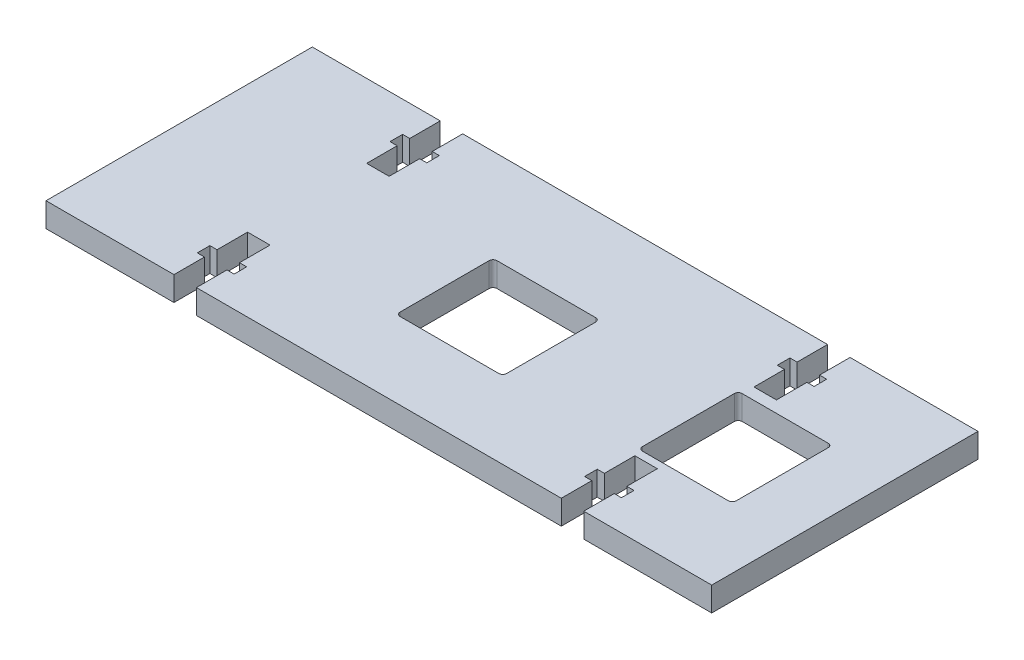
SolidWorks part; units mm, degrees
ref_plane "Front Plane" through (0, 0, 0) normal (0, 0, 1) x (1, 0, 0)
ref_plane "Top Plane" through (0, 0, 0) normal (0, 1, 0) x (1, 0, 0)
ref_plane "Right Plane" through (0, 0, 0) normal (1, 0, 0) x (0, 0, -1)
sketch "Sketch1" plane through (0, 0, 0) normal (0, 1, 0) x (1, 0, 0)
  line L1 (-43.6562, -17.4625) -> (43.6563, -17.4625)
  line L2 (-43.6562, -17.4625) -> (-43.6562, 17.4625)
  line L3 (-43.6562, 17.4625) -> (43.6563, 17.4625)
  line L4 (43.6563, -17.4625) -> (43.6563, 17.4625)
  line L5 (-43.6562, -17.4625) -> (43.6563, 17.4625) construction
  line L6 (-43.6562, 17.4625) -> (43.6563, -17.4625) construction
  point P0 (0, 0)
  dimension "D1" = 87.3125
  dimension "D2" = 34.925
extrude "Boss-Extrude1" add sketch "Sketch1" along normal blind 3.175
sketch "Sketch3" plane through (0, 0, 0) normal (0, -1, 0) x (1, 0, 0)
  line L0 (-43.6562, 17.4625) -> (43.6563, 17.4625) construction
  line L1 (-26.8732, 17.4625) -> (-23.9268, 17.4625)
  line L2 (-26.8732, 17.4625) -> (-26.8732, 13.462)
  line L3 (-26.8732, 7.8105) -> (-23.9268, 7.8105)
  line L4 (-23.9268, 17.4625) -> (-23.9268, 13.462)
  line L5 (-26.8732, 17.4625) -> (-23.9268, 7.8105) construction
  line L6 (-26.8732, 13.462) -> (-27.813, 13.462)
  line L7 (-22.987, 11.811) -> (-23.9268, 11.811)
  line L8 (-22.987, 11.811) -> (-22.987, 13.462)
  line L9 (-22.987, 13.462) -> (-23.9268, 13.462)
  line L10 (-27.813, 11.811) -> (-27.813, 13.462)
  line L11 (-22.987, 11.811) -> (-27.813, 13.462) construction
  line L12 (-22.987, 13.462) -> (-27.813, 11.811) construction
  line L13 (-23.9268, 11.811) -> (-23.9268, 7.8105)
  line L14 (-26.8732, 11.811) -> (-27.813, 11.811)
  line L15 (-26.8732, 11.811) -> (-26.8732, 7.8105)
  line L16 (-25.4, 7.8105) -> (-25.4, 17.4625) construction
  line L17 (0, 17.4625) -> (0, -17.4625) construction
  line L18 (43.6563, -17.4625) -> (-43.6562, -17.4625) construction
  line L19 (25.4, 7.8105) -> (25.4, 17.4625) construction
  line L20 (22.987, 13.462) -> (27.813, 11.811) construction
  line L21 (22.987, 11.811) -> (27.813, 13.462) construction
  line L22 (26.8732, 17.4625) -> (23.9268, 7.8105) construction
  line L23 (26.8732, 11.811) -> (26.8732, 7.8105)
  line L24 (26.8732, 11.811) -> (27.813, 11.811)
  line L25 (23.9268, 11.811) -> (23.9268, 7.8105)
  line L26 (27.813, 11.811) -> (27.813, 13.462)
  line L27 (22.987, 13.462) -> (23.9268, 13.462)
  line L28 (22.987, 11.811) -> (22.987, 13.462)
  line L29 (22.987, 11.811) -> (23.9268, 11.811)
  line L30 (26.8732, 13.462) -> (27.813, 13.462)
  line L31 (23.9268, 17.4625) -> (23.9268, 13.462)
  line L32 (26.8732, 7.8105) -> (23.9268, 7.8105)
  line L33 (26.8732, 17.4625) -> (26.8732, 13.462)
  line L34 (26.8732, 17.4625) -> (23.9268, 17.4625)
  line L35 (-43.6562, 0) -> (-37.7203, 0) construction
  line L36 (-43.6562, -17.4625) -> (-43.6562, 17.4625) construction
  line L37 (26.8732, -17.4625) -> (23.9268, -7.8105) construction
  line L38 (22.987, -11.811) -> (27.813, -13.462) construction
  line L39 (22.987, -13.462) -> (27.813, -11.811) construction
  line L40 (25.4, -7.8105) -> (25.4, -17.4625) construction
  line L41 (26.8732, -17.4625) -> (23.9268, -17.4625)
  line L42 (26.8732, -17.4625) -> (26.8732, -13.462)
  line L43 (26.8732, -7.8105) -> (23.9268, -7.8105)
  line L44 (23.9268, -17.4625) -> (23.9268, -13.462)
  line L45 (26.8732, -13.462) -> (27.813, -13.462)
  line L46 (22.987, -11.811) -> (23.9268, -11.811)
  line L47 (22.987, -11.811) -> (22.987, -13.462)
  line L48 (22.987, -13.462) -> (23.9268, -13.462)
  line L49 (27.813, -11.811) -> (27.813, -13.462)
  line L50 (23.9268, -11.811) -> (23.9268, -7.8105)
  line L51 (26.8732, -11.811) -> (27.813, -11.811)
  line L52 (26.8732, -11.811) -> (26.8732, -7.8105)
  line L53 (-25.4, -7.8105) -> (-25.4, -17.4625) construction
  line L54 (-22.987, -13.462) -> (-27.813, -11.811) construction
  line L55 (-22.987, -11.811) -> (-27.813, -13.462) construction
  line L56 (-26.8732, -17.4625) -> (-23.9268, -7.8105) construction
  line L57 (-26.8732, -11.811) -> (-26.8732, -7.8105)
  line L58 (-26.8732, -11.811) -> (-27.813, -11.811)
  line L59 (-23.9268, -11.811) -> (-23.9268, -7.8105)
  line L60 (-27.813, -11.811) -> (-27.813, -13.462)
  line L61 (-22.987, -13.462) -> (-23.9268, -13.462)
  line L62 (-22.987, -11.811) -> (-22.987, -13.462)
  line L63 (-22.987, -11.811) -> (-23.9268, -11.811)
  line L64 (-26.8732, -13.462) -> (-27.813, -13.462)
  line L65 (-23.9268, -17.4625) -> (-23.9268, -13.462)
  line L66 (-26.8732, -7.8105) -> (-23.9268, -7.8105)
  line L67 (-26.8732, -17.4625) -> (-26.8732, -13.462)
  line L68 (-26.8732, -17.4625) -> (-23.9268, -17.4625)
  point P6 (-25.4, 12.6365)
  point P18 (-25.4, 12.6365)
  point P36 (25.4, 12.6365)
  point P56 (25.4, -12.6365)
  point P71 (-25.4, -12.6365)
  dimension "D1" = 9.652
  dimension "D2" = 2.9464
  dimension "D3" = 1.651
  dimension "D4" = 4.826
  dimension "D5" = 25.4
extrude "Cut-Extrude2" cut sketch "Sketch3" against normal through all
sketch "Sketch4" plane through (0, 0, 0) normal (0, -1, 0) x (-1, 0, 0)
  line L0 (0.8075, -1.9108) -> (0.8075, -0.1762) construction
  line L1 (3.6075, -1.0435) -> (0.8075, -1.0435) construction
  line L2 (7.7925, 5.3065) -> (-6.1775, 5.3065)
  line L3 (7.7925, 5.3065) -> (7.7925, -7.3935)
  line L4 (7.7925, -7.3935) -> (-6.1775, -7.3935)
  line L5 (-6.1775, 5.3065) -> (-6.1775, -7.3935)
  line L6 (7.7925, 5.3065) -> (-6.1775, -7.3935) construction
  line L7 (7.7925, -7.3935) -> (-6.1775, 5.3065) construction
  line L8 (-23.3845, -6.7945) -> (-35.6905, -6.7945)
  line L10 (-23.3845, -6.7945) -> (-23.3845, 6.2865)
  line L11 (-23.3845, 6.2865) -> (-35.6905, 6.2865)
  line L12 (-35.6905, -6.7945) -> (-35.6905, 6.2865)
  line L13 (-25.8147, -6.7945) -> (-35.6905, 6.2865) construction
  line L14 (-23.3845, 6.2865) -> (-33.2603, -6.7945) construction
  line L15 (-23.9268, -7.8105) -> (-26.8732, -7.8105) construction
  point P2 (0.8075, -1.0435)
  point P10 (-29.5375, -1.8635)
  dimension "D1" = 13.97
  dimension "D2" = 12.7
  dimension "D3" = 1.016
extrude "Cut-Extrude3" cut sketch "Sketch4" against normal through all
fillet "Fillet1" radius 0.508 8 edges at (35.6905, 1.5875, -6.2865) (23.3845, 1.5875, -6.2865) (-7.7925, 1.5875, -5.3065) (6.1775, 1.5875, -5.3065) (6.1775, 1.5875, 7.3935) (-7.7925, 1.5875, 7.3935) (35.6905, 1.5875, 6.7945) (23.3845, 1.5875, 6.7945)
